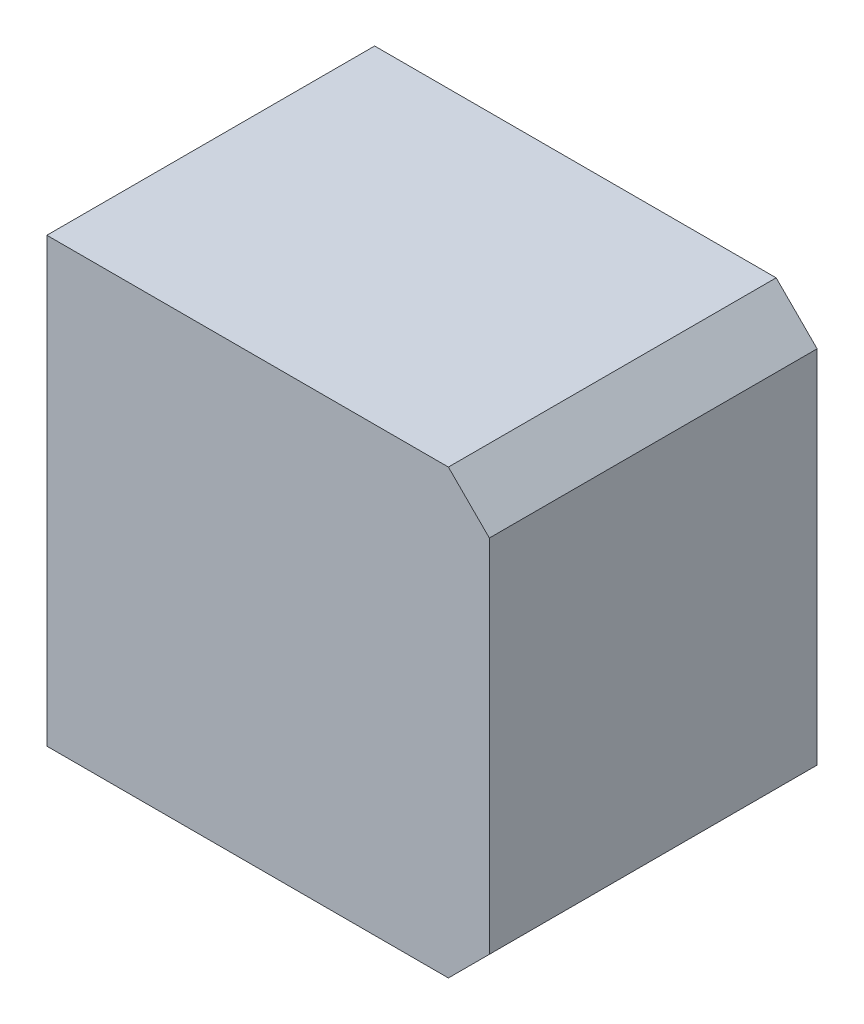
SolidWorks part; units mm, degrees
ref_plane "前视基准面" through (0, 0, 0) normal (0, 0, 1) x (1, 0, 0)
ref_plane "上视基准面" through (0, 0, 0) normal (0, 1, 0) x (1, 0, 0)
ref_plane "右视基准面" through (0, 0, 0) normal (1, 0, 0) x (0, 0, -1)
sketch "草图1" plane through (0, 0, 0) normal (0, 0, 1) x (1, 0, 0)
  line L1 (-5.4, -5.4) -> (5.4, -5.4)
  line L2 (-5.4, -5.4) -> (-5.4, 5.4)
  line L3 (-5.4, 5.4) -> (5.4, 5.4)
  line L4 (5.4, -5.4) -> (5.4, 5.4)
  line L5 (-5.4, -5.4) -> (5.4, 5.4) construction
  line L6 (-5.4, 5.4) -> (5.4, -5.4) construction
  point P0 (0, 0)
  dimension "D1" = 10.8
  dimension "D2" = 10.8
extrude "凸台-拉伸1" add sketch "草图1" along normal mid plane 8 contours L4 L3 L2 L1
chamfer "倒角1" distance 1 angle 45 2 edges at (5.4, 5.4, 0) (5.4, -5.4, 0)
